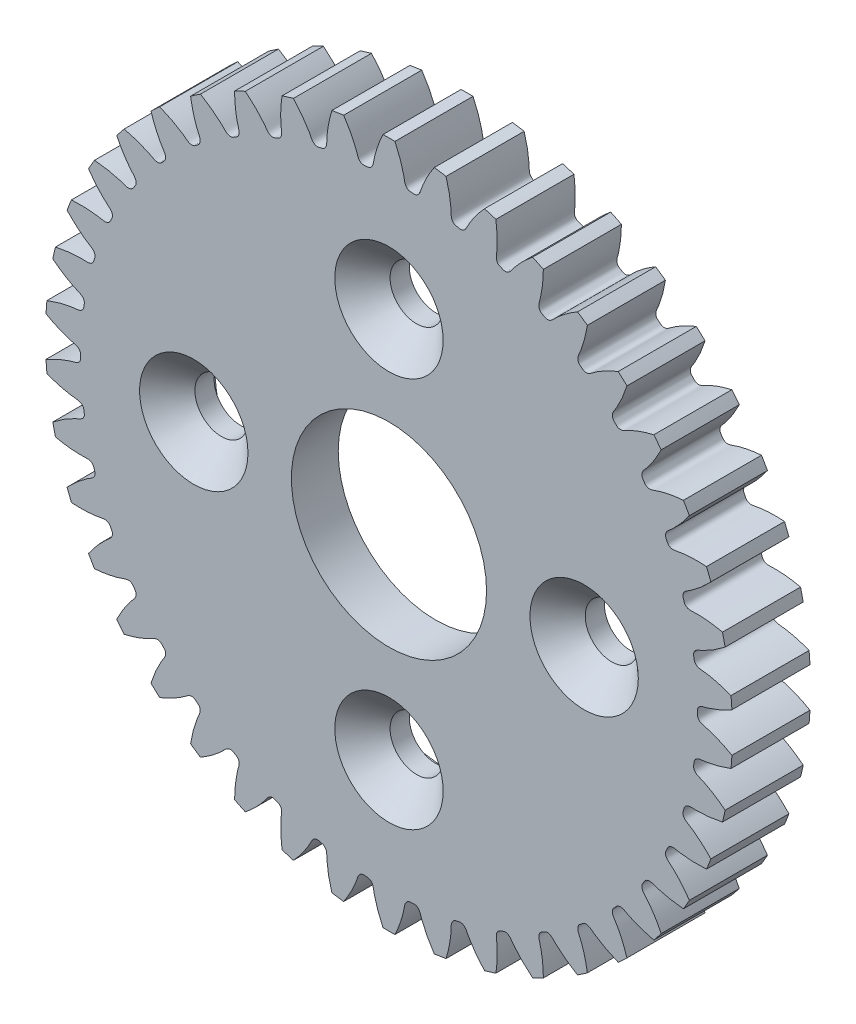
SolidWorks part; units mm, degrees
ref_plane "Front Plane" through (0, 0, 0) normal (0, 0, 1) x (1, 0, 0)
ref_plane "Top Plane" through (0, 0, 0) normal (0, 1, 0) x (1, 0, 0)
ref_plane "Right Plane" through (0, 0, 0) normal (1, 0, 0) x (0, 0, -1)
ref_axis "Axis1" through (0, 0, 55) along (0, 0, -1)
sketch "SketchRevolveSpurAssem30-42M1Gear" plane through (0, 0, 0) normal (1, 0, 0) x (0, 0, -1)
  line L0 (0, 0) -> (1, 0) construction
  line L1 (-2.5, 0) -> (-2.5, 22)
  line L2 (-2.5, 22) -> (2.5, 22)
  line L3 (2.5, 22) -> (2.5, 0)
  line L4 (2.5, 0) -> (-2.5, 0)
  dimension "Side1" = 2.5
  dimension "OutsideRadius" = 22
  dimension "Side2" = 2.5
revolve "SpurAssem30-42M1Gear" add sketch "SketchRevolveSpurAssem30-42M1Gear" angle 360 about L0
sketch "SketchToothSpurAssem30-42M1Gear" plane through (0, 0, 0) normal (0, 0, 1) x (1, 0, 0)
  arc A0 (22.0122, 1.2905) -> (22.0122, -1.2905) centre (0, 0) cw
  spline S0 degree 3 poles (22.0122, -1.2905) (21.8769, -1.2128) (21.6972, -1.1153) (21.4727, -1.0033) (21.3469, -0.9431) (21.225, -0.8873) (21.1073, -0.8358) (20.9938, -0.7883) (20.8847, -0.7448) (20.7799, -0.7051) (20.6797, -0.669) (20.5841, -0.6363) (20.4933, -0.6069) (20.4072, -0.5807) (20.3259, -0.5575) (20.2198, -0.5284) (20.1313, -0.5099) (20.0625, -0.4876) (20.0388, -0.4791) (20.0153, -0.4697) (19.992, -0.4593) (19.9687, -0.4477) (19.9453, -0.4347) (19.9217, -0.4198) (19.8977, -0.4026) (19.8734, -0.3825) (19.8488, -0.3588) (19.8244, -0.3305) (19.8009, -0.2968) (19.7797, -0.2571) (19.7626, -0.2112) (19.7521, -0.1625) (19.7479, -0.0914) (19.7515, 0) (19.7479, 0.0914) (19.7521, 0.1625) (19.7626, 0.2112) (19.7797, 0.2571) (19.8009, 0.2968) (19.8244, 0.3305) (19.8488, 0.3588) (19.8734, 0.3825) (19.8977, 0.4026) (19.9217, 0.4198) (19.9453, 0.4347) (19.9687, 0.4477) (19.992, 0.4593) (20.0153, 0.4697) (20.0388, 0.4791) (20.0625, 0.4876) (20.1313, 0.5099) (20.2198, 0.5284) (20.3259, 0.5575) (20.4072, 0.5807) (20.4933, 0.6069) (20.5841, 0.6363) (20.6797, 0.669) (20.7799, 0.7051) (20.8847, 0.7448) (20.9938, 0.7883) (21.1073, 0.8358) (21.225, 0.8873) (21.3469, 0.9431) (21.4727, 1.0033) (21.6972, 1.1153) (21.8769, 1.2128) (22.0122, 1.2905) knots 0 0 0 0 0.085044 0.111394 0.136744 0.161094 0.184444 0.206795 0.228146 0.248498 0.267849 0.286201 0.303554 0.319906 0.335259 0.349613 0.37987 0.384459 0.389028 0.393607 0.398229 0.402938 0.407785 0.412834 0.41816 0.423854 0.430019 0.436764 0.444188 0.452354 0.461253 0.470759 0.47943 0.5 0.52057 0.529241 0.538747 0.547646 0.555812 0.563236 0.569981 0.576146 0.58184 0.587166 0.592215 0.597062 0.601771 0.606393 0.610972 0.615541 0.62013 0.650387 0.664741 0.680094 0.696446 0.713799 0.732151 0.751502 0.771854 0.793205 0.815556 0.838906 0.863256 0.888606 0.914956 1 1 1 1
extrude "ToothExtrudeCutSpurAssem30-42M1Gear" cut sketch "SketchToothSpurAssem30-42M1Gear" against normal blind 2.5 and the other way blind 2.5
pattern_circular "PatternSpurAssem30-42M1Gear" count 42 every 8.571 about axis through (0, 0, 55) along (0, 0, -1) of "ToothExtrudeCutSpurAssem30-42M1Gear"
sketch "BoreRevolveSketch" plane through (0, 0, 0) normal (1, 0, 0) x (0, 0, -1)
  line L0 (0, 0) -> (1, 0) construction
  line L1 (-2.5, 0) -> (2.5, 0)
  line L2 (2.5, 0) -> (2.5, 2.5)
  line L3 (2.5, 2.5) -> (-2.5, 2.5)
  line L4 (-2.5, 2.5) -> (-2.5, 0)
  dimension "BoreSide1" = 2.5
  dimension "TaperSide1" = 2.5
  dimension "BoreSide2" = 2.5
  dimension "TaperSide2" = 2.5
revolve "BoreRevolveCut" cut sketch "BoreRevolveSketch" angle 360 about L0
sketch "AuxiliarySketchSpurAssem30-42M1Gear" plane through (0, 0, 0) normal (0, 0, 1) x (1, 0, 0)
  circle A0 centre (0, 0) radius 21 construction
  circle A1 centre (0, 0) radius 19.7335 construction
  circle A2 centre (0, 0) radius 20.1559 construction
  circle A3 centre (0, 0) radius 22 construction
  circle A4 centre (0, 0) radius 19.75 construction
  dimension "PitchDiameter" = 42
  dimension "BaseDiameter" = 39.4671
  dimension "FormDiameter" = 40.3119
  dimension "MajorDiameter" = 44
  dimension "MinorDiameter" = 39.5
sketch "Sketch1" plane through (0, 0, -2.5) normal (0, 0, -1) x (-1, 0, 0)
  circle A0 centre (0, 0) radius 16.25
  dimension "D1" = 32.5
extrude "Cut-Extrude1" cut sketch "Sketch1" against normal blind 2
sketch "Sketch2" plane through (0, 0, 2.5) normal (0, 0, 1) x (1, 0, 0)
  circle A0 centre (0, 0) radius 12.5 construction
  dimension "D1" = 25
hole_wizard "CSK for M3 Hex Socket Countersunk Head Screw1" positions "Sketch3" profile "Sketch4" countersink size "M3" standard "DIN" end condition through all
sketch "Sketch3" plane through (0, 0, 2.5) normal (0, 0, 1) x (1, 0, 0)
  circle A0 centre (0, 0) radius 12.5 construction
  point P0 (0, 12.5)
  point P4 (-12.5, 0)
  point P6 (0, -12.5)
  point P8 (12.5, 0)
sketch "Sketch4" plane through (0, 12.5, 2.5) normal (1, 0, 0) x (0, -1, 0)
  line L0 (0, 0) -> (0, 5)
  line L1 (0, 5) -> (1.7, 5)
  line L2 (1.7, 5) -> (1.7, 1.77)
  line L3 (1.7, 1.77) -> (3.47, 0)
  line L5 (3.47, 0) -> (0, 0)
  line L6 (-1.7, 1.77) -> (-3.47, 0) construction
  line L11 (0, -6.35) -> (0, 107.95) construction
  dimension "Thru Hole Dia." = 3.4
  dimension "Thru Hole Depth" = 5
  dimension "Near C'Sink Dia." = 6.94
  dimension "Near C'Sink Angle" = 90
sketch "Sketch5" plane through (0, 0, 2.5) normal (0, 0, 1) x (1, 0, 0)
  circle A0 centre (0, 0) radius 6.25
  dimension "D1" = 12.5
extrude "Cut-Extrude2" cut sketch "Sketch5" against normal blind 10
